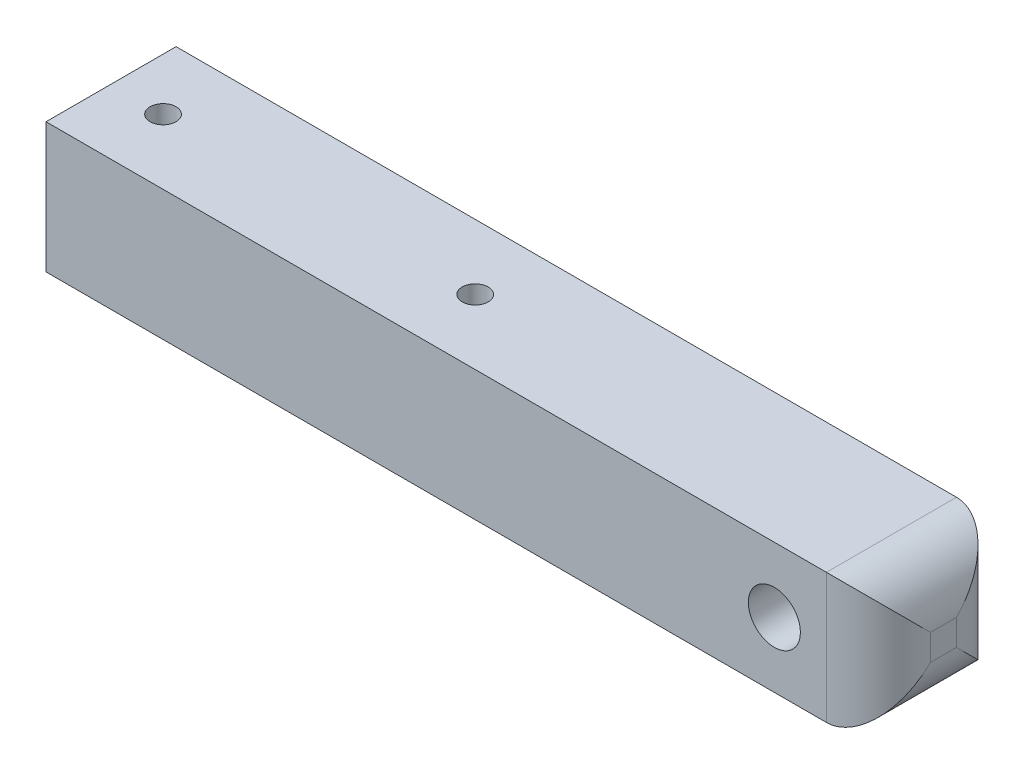
SolidWorks part; units mm, degrees
ref_plane "Front Plane" through (0, 0, 0) normal (0, 0, 1) x (1, 0, 0)
ref_plane "Top Plane" through (0, 0, 0) normal (0, 1, 0) x (1, 0, 0)
ref_plane "Right Plane" through (0, 0, 0) normal (1, 0, 0) x (0, 0, -1)
sketch "Sketch1" plane through (0, 0, 0) normal (0, 0, 1) x (1, 0, 0)
  line L0 (0, 0) -> (101.6, 0)
  line L1 (101.6, 0) -> (101.6, 31.75)
  line L2 (101.6, 31.75) -> (-101.6, 31.75)
  line L3 (-101.6, 31.75) -> (-101.6, 0)
  line L4 (-101.6, 0) -> (0, 0)
  dimension "D1" = 31.75
  dimension "D2" = 203.2
extrude "Boss-Extrude1" add sketch "Sketch1" along normal mid plane 31.75
sketch "Sketch2" plane through (-101.6, 0, 0) normal (-1, 0, 0) x (0, 0, 1)
  line L0 (0, 4.9711) -> (-8.9803, 13.9513)
  line L1 (-8.9803, 13.9513) -> (-9.8783, 13.0533)
  line L2 (-9.8783, 13.0533) -> (0, 3.175)
  line L3 (0, 3.175) -> (9.8783, 13.0533)
  line L4 (9.8783, 13.0533) -> (8.9803, 13.9513)
  line L5 (8.9803, 13.9513) -> (0, 4.9711)
  line L6 (-11.3146, 0) -> (21.0706, 0) construction
  line L7 (-15.875, 31.75) -> (-15.875, 0) construction
  line L8 (-9.8783, 13.0533) -> (-15.875, 13.0533) construction
  line L9 (9.8783, 13.0533) -> (15.875, 13.0533) construction
  line L10 (15.875, 31.75) -> (15.875, 0) construction
  dimension "D1" = 1.27
  dimension "D2" = 3.175
  dimension "D3" = 12.7
extrude "Cut-Extrude1" cut sketch "Sketch2" against normal blind 152.4
hole_wizard "1/2 (0.5) Diameter Hole1" positions "Sketch3" profile "Sketch4" hole size "1/2" standard "ANSI Inch" end condition through all
sketch "Sketch3" plane through (0, 0, 15.875) normal (0, 0, 1) x (1, 0, 0)
  line L0 (-101.6, 31.75) -> (-101.6, 0) construction
  line L1 (-101.6, 15.875) -> (162.3719, 15.875) construction
  point P0 (76.2, 15.875)
  point P13 (-38.1, 15.875)
  point P14 (162.3719, 15.875)
  dimension "D1" = 177.8
sketch "Sketch4" plane through (76.2, 15.875, 15.875) normal (1, 0, 0) x (0, -1, 0)
  line L0 (0, 0) -> (0, 31.75)
  line L1 (0, 31.75) -> (6.35, 31.75)
  line L2 (6.35, 31.75) -> (6.35, 0)
  line L5 (6.35, 0) -> (0, 0)
  line L11 (0, -6.35) -> (0, 107.95) construction
  dimension "Thru Hole Dia." = 12.7
  dimension "Thru Hole Depth" = 31.75
hole_wizard "1/4 (0.25) Diameter Hole1" positions "Sketch5" profile "Sketch6" hole size "1/4" standard "ANSI Inch" end condition through all
sketch "Sketch5" plane through (0, 31.75, 0) normal (0, 1, 0) x (1, 0, 0)
  line L0 (-101.6, -15.875) -> (-101.6, 15.875) construction
  point P0 (-88.9, 0)
  point P2 (-12.7, 0)
  point P5 (0, 0)
  point P7 (-12.7, 0)
  dimension "D1" = 12.7
  dimension "D2" = 76.2
sketch "Sketch6" plane through (-88.9, 31.75, 0) normal (1, 0, 0) x (0, 0, 1)
  line L0 (0, 0) -> (0, 31.75)
  line L1 (0, 31.75) -> (3.175, 31.75)
  line L2 (3.175, 31.75) -> (3.175, 0)
  line L5 (3.175, 0) -> (0, 0)
  line L11 (0, -6.35) -> (0, 107.95) construction
  dimension "Thru Hole Dia." = 6.35
  dimension "Thru Hole Depth" = 31.75
fillet "Fillet1" radius 12.7 4 edges at (101.6, 0, 0) (101.6, 15.875, -15.875) (101.6, 31.75, 0) (101.6, 15.875, 15.875)
